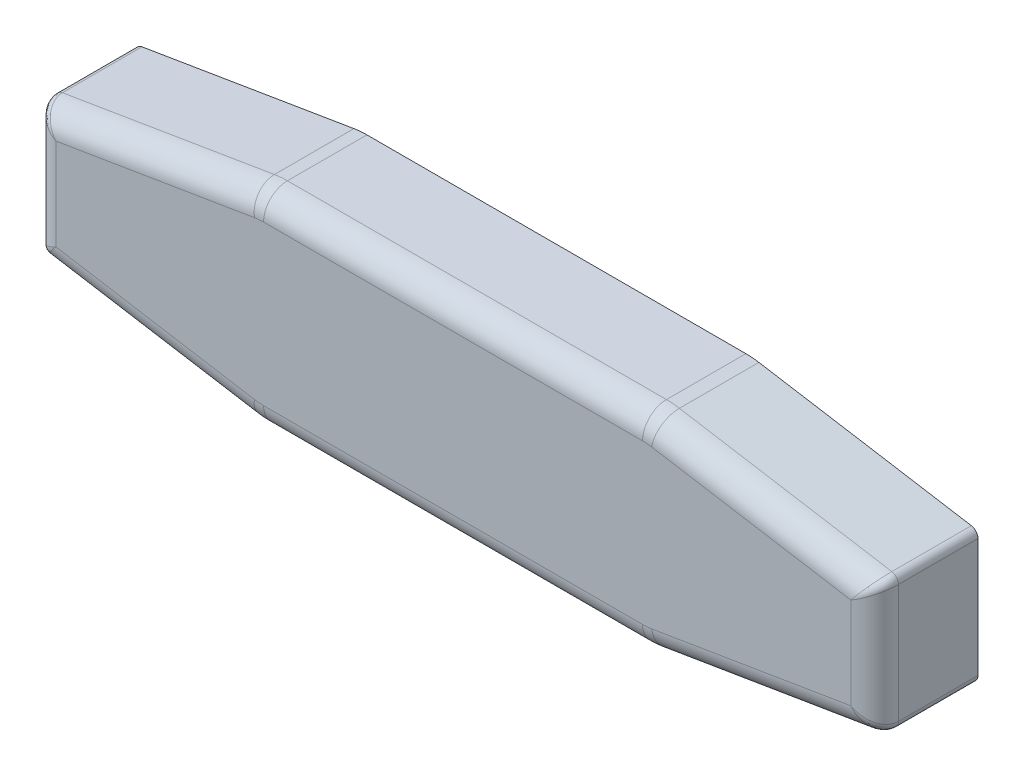
SolidWorks part; units mm, degrees
material "moto_glass"
ref_plane "Front Plane" through (0, 0, 0) normal (0, 0, 1) x (1, 0, 0)
ref_plane "Top Plane" through (0, 0, 0) normal (0, 1, 0) x (1, 0, 0)
ref_plane "Right Plane" through (0, 0, 0) normal (1, 0, 0) x (0, 0, -1)
sketch "Sketch1" plane through (0, 0, 0) normal (0, 0, 1) x (1, 0, 0)
  line L12 (-24.854, 15) -> (-55, 10)
  line L14 (55, 10) -> (24.7913, 15)
  line L16 (-24.854, 15) -> (24.7913, 15)
  line L25 (0, 0) -> (4.6771, 0)
  line L26 (55, -10) -> (24.7913, -15)
  line L27 (-24.854, -15) -> (24.7913, -15)
  line L28 (-24.854, -15) -> (-55, -10)
  line L29 (-24.6892, 13) -> (-53, 8.3044)
  line L30 (-53, 8.3044) -> (-53, -8.3044)
  line L31 (-24.6892, -13) -> (-53, -8.3044)
  line L32 (-24.6892, -13) -> (24.6269, -13)
  line L33 (53, -8.3038) -> (24.6269, -13)
  line L34 (53, 8.3038) -> (53, -8.3038)
  line L35 (53, 8.3038) -> (24.6269, 13)
  line L36 (-55, 10) -> (-55, -10)
  line L37 (55, 10) -> (55, -10)
  line L38 (-24.6892, 13) -> (24.6269, 13)
  line L39 (-24.6069, 12) -> (-52, 7.4566)
  line L40 (-52, 7.4566) -> (-52, -7.4566)
  line L41 (-24.6069, -12) -> (-52, -7.4566)
  line L42 (-24.6069, -12) -> (24.5447, -12)
  line L43 (52, -7.4557) -> (24.5447, -12)
  line L44 (52, 7.4557) -> (52, -7.4557)
  line L45 (52, 7.4557) -> (24.5447, 12)
  line L46 (-24.6069, 12) -> (24.5447, 12)
  line L47 (-24.6069, 12) -> (-24.6069, -12)
  line L48 (6.6929, 12) -> (6.6929, -12)
  line L49 (-23.6069, 12) -> (-23.6069, -12)
  line L50 (-25.6069, 11.8341) -> (-25.6069, -11.8341)
  line L51 (0, 0) -> (0, 3.5519)
  line L52 (-7.6929, 12) -> (-7.6929, -12)
  line L53 (-8.6929, 12) -> (-8.6929, -12)
  line L54 (-9.6929, 12) -> (-9.6929, -12)
  line L55 (-10.6929, 12) -> (-10.6929, -12)
  line L56 (-11.6929, 12) -> (-11.6929, -12)
  line L57 (-12.6929, 12) -> (-12.6929, -12)
  line L58 (-13.6929, 12) -> (-13.6929, -12)
  line L59 (-14.6929, 12) -> (-14.6929, -12)
  line L60 (-15.6929, 12) -> (-15.6929, -12)
  line L61 (-16.6929, 12) -> (-16.6929, -12)
  line L62 (-17.6929, 12) -> (-17.6929, -12)
  line L63 (-18.6929, 12) -> (-18.6929, -12)
  line L64 (-19.6929, 12) -> (-19.6929, -12)
  line L65 (-20.6929, 12) -> (-20.6929, -12)
  line L66 (-21.6929, 12) -> (-21.6929, -12)
  line L67 (-22.6929, 12) -> (-22.6929, -12)
  line L68 (-26.6069, 11.6683) -> (-26.6069, -11.6683)
  line L69 (-27.6069, 11.5024) -> (-27.6069, -11.5024)
  line L70 (-28.6069, 11.3366) -> (-28.6069, -11.3366)
  line L71 (-29.6069, 11.1707) -> (-29.6069, -11.1707)
  line L72 (-30.6069, 11.0048) -> (-30.6069, -11.0048)
  line L73 (-31.6069, 10.839) -> (-31.6069, -10.839)
  line L74 (-32.6069, 10.6731) -> (-32.6069, -10.6731)
  line L75 (-33.6069, 10.5073) -> (-33.6069, -10.5073)
  line L76 (-34.6069, 10.3414) -> (-34.6069, -10.3414)
  line L77 (-35.6069, 10.1755) -> (-35.6069, -10.1755)
  line L78 (-36.6069, 10.0097) -> (-36.6069, -10.0097)
  line L79 (-37.6069, 9.8438) -> (-37.6069, -9.8438)
  line L80 (-38.6069, 9.678) -> (-38.6069, -9.678)
  line L81 (-39.6069, 9.5121) -> (-39.6069, -9.5121)
  line L82 (-40.6069, 9.3463) -> (-40.6069, -9.3463)
  line L83 (-41.6069, 9.1804) -> (-41.6069, -9.1804)
  line L84 (-42.6069, 9.0145) -> (-42.6069, -9.0145)
  line L85 (-43.6069, 8.8487) -> (-43.6069, -8.8487)
  line L86 (-44.6069, 8.6828) -> (-44.6069, -8.6828)
  line L87 (-45.6069, 8.517) -> (-45.6069, -8.517)
  line L88 (-46.6069, 8.3511) -> (-46.6069, -8.3511)
  line L89 (-47.6069, 8.1852) -> (-47.6069, -8.1852)
  line L90 (-48.6069, 8.0194) -> (-48.6069, -8.0194)
  line L91 (-49.6069, 7.8535) -> (-49.6069, -7.8535)
  line L92 (-50.6069, 7.6877) -> (-50.6069, -7.6877)
  line L93 (-51.6069, 7.5218) -> (-51.6069, -7.5218)
  line L94 (-6.6929, 12) -> (-6.6929, -12)
  line L95 (-5.6929, 12) -> (-5.6929, -12)
  line L96 (-4.6929, 12) -> (-4.6929, -12)
  line L97 (-3.6929, 12) -> (-3.6929, -12)
  line L98 (-2.6929, 12) -> (-2.6929, -12)
  line L99 (-1.6929, 12) -> (-1.6929, -12)
  line L100 (-0.6929, 12) -> (-0.6929, -12)
  line L101 (5.6929, 12) -> (5.6929, -12)
  line L102 (4.6929, 12) -> (4.6929, -12)
  line L103 (3.6929, 12) -> (3.6929, -12)
  line L104 (24.6069, 12) -> (-24.5447, 12)
  line L105 (-52, 7.4557) -> (-24.5447, 12)
  line L106 (-52, 7.4557) -> (-52, -7.4557)
  line L107 (-52, -7.4557) -> (-24.5447, -12)
  line L108 (24.6069, -12) -> (-24.5447, -12)
  line L109 (24.6069, -12) -> (52, -7.4566)
  line L110 (52, 7.4566) -> (52, -7.4566)
  line L111 (24.6069, 12) -> (52, 7.4566)
  line L112 (2.6929, 12) -> (2.6929, -12)
  line L113 (1.6929, 12) -> (1.6929, -12)
  line L114 (0.6929, 12) -> (0.6929, -12)
  line L115 (7.6929, 12) -> (7.6929, -12)
  line L116 (8.6929, 12) -> (8.6929, -12)
  line L117 (9.6929, 12) -> (9.6929, -12)
  line L118 (10.6929, 12) -> (10.6929, -12)
  line L119 (11.6929, 12) -> (11.6929, -12)
  line L120 (12.6929, 12) -> (12.6929, -12)
  line L121 (13.6929, 12) -> (13.6929, -12)
  line L122 (14.6929, 12) -> (14.6929, -12)
  line L123 (15.6929, 12) -> (15.6929, -12)
  line L124 (16.6929, 12) -> (16.6929, -12)
  line L125 (17.6929, 12) -> (17.6929, -12)
  line L126 (18.6929, 12) -> (18.6929, -12)
  line L127 (19.6929, 12) -> (19.6929, -12)
  line L128 (20.6929, 12) -> (20.6929, -12)
  line L129 (21.6929, 12) -> (21.6929, -12)
  line L130 (22.6929, 12) -> (22.6929, -12)
  line L131 (23.6069, 12) -> (23.6069, -12)
  line L132 (24.6069, 12) -> (24.6069, -12)
  line L133 (25.6069, 11.8341) -> (25.6069, -11.8341)
  line L134 (26.6069, 11.6683) -> (26.6069, -11.6683)
  line L135 (27.6069, 11.5024) -> (27.6069, -11.5024)
  line L136 (28.6069, 11.3366) -> (28.6069, -11.3366)
  line L137 (29.6069, 11.1707) -> (29.6069, -11.1707)
  line L138 (30.6069, 11.0048) -> (30.6069, -11.0048)
  line L139 (31.6069, 10.839) -> (31.6069, -10.839)
  line L140 (32.6069, 10.6731) -> (32.6069, -10.6731)
  line L141 (33.6069, 10.5073) -> (33.6069, -10.5073)
  line L142 (34.6069, 10.3414) -> (34.6069, -10.3414)
  line L143 (35.6069, 10.1755) -> (35.6069, -10.1755)
  line L144 (36.6069, 10.0097) -> (36.6069, -10.0097)
  line L145 (37.6069, 9.8438) -> (37.6069, -9.8438)
  line L146 (38.6069, 9.678) -> (38.6069, -9.678)
  line L147 (39.6069, 9.5121) -> (39.6069, -9.5121)
  line L148 (40.6069, 9.3463) -> (40.6069, -9.3463)
  line L149 (41.6069, 9.1804) -> (41.6069, -9.1804)
  line L150 (42.6069, 9.0145) -> (42.6069, -9.0145)
  line L151 (43.6069, 8.8487) -> (43.6069, -8.8487)
  line L152 (44.6069, 8.6828) -> (44.6069, -8.6828)
  line L153 (45.6069, 8.517) -> (45.6069, -8.517)
  line L154 (46.6069, 8.3511) -> (46.6069, -8.3511)
  line L155 (47.6069, 8.1852) -> (47.6069, -8.1852)
  line L156 (48.6069, 8.0194) -> (48.6069, -8.0194)
  line L157 (49.6069, 7.8535) -> (49.6069, -7.8535)
  line L158 (50.6069, 7.6877) -> (50.6069, -7.6877)
  line L159 (51.6069, 7.5218) -> (51.6069, -7.5218)
  point P3 (-55, 0)
  point P7 (55, 0)
  dimension "D1" = 10
  dimension "D2" = 10
  dimension "D3" = 15
  dimension "D4" = 2
  dimension "D5" = 1
  dimension "D6" = 1
  dimension "D7" = 1
  dimension "D8" = 1
  dimension "D9" = 1
  dimension "D10" = 1
  dimension "D11" = 1
  dimension "D12" = 1
  dimension "D13" = 1
  dimension "D14" = 1
  dimension "D15" = 1
  dimension "D16" = 1
  dimension "D17" = 1
  dimension "D18" = 1
  dimension "D19" = 1
  dimension "D20" = 1
  dimension "D21" = 1
  dimension "D22" = 1
  dimension "D23" = 1
  dimension "D24" = 1
  dimension "D25" = 1
  dimension "D26" = 1
  dimension "D27" = 1
  dimension "1" = 1
  dimension "D28" = 1
  dimension "D29" = 1
  dimension "D30" = 1
  dimension "D31" = 1
  dimension "D32" = 1
  dimension "D33" = 1
  dimension "D34" = 1
  dimension "D35" = 1
  dimension "D36" = 1
  dimension "D37" = 1
  dimension "D38" = 1
  dimension "D39" = 1
  dimension "D40" = 1
  dimension "D41" = 1
  dimension "D42" = 1
  dimension "D43" = 1
  dimension "D44" = 1
  dimension "D45" = 1
  dimension "D46" = 1
  dimension "D47" = 1
  dimension "D48" = 1
  dimension "D49" = 1
  dimension "D50" = 1
  dimension "D51" = 1
  dimension "D52" = 1
  dimension "D54" = 1
  dimension "D55" = 1
extrude "Boss-Extrude5" add sketch "Sketch1" along normal blind 13 contours L38 L29 L30 L31 L32 L33 L34 L35 L104 L111 L110 L44 L109 region at (-0.0312, 12.8909, 0)
sketch "Sketch4" plane through (0, 0, 13) normal (0, 0, 1) x (1, 0, 0)
  line L16 (52, 7.4566) -> (24.6069, 12)
  line L17 (52, -7.4566) -> (52, 7.4566)
  line L18 (24.6069, -12) -> (52, -7.4566)
  line L19 (-24.6069, -12) -> (24.6069, -12)
  line L20 (-52, -7.4566) -> (-24.6069, -12)
  line L21 (-52, 7.4566) -> (-52, -7.4566)
  line L22 (-24.6069, 12) -> (-52, 7.4566)
  line L23 (24.6069, 12) -> (-24.6069, 12)
  line L24 (52, 7.4566) -> (24.6069, 12)
  line L25 (52, -7.4566) -> (52, 7.4566)
  line L26 (24.6069, -12) -> (52, -7.4566)
  line L27 (-24.6069, -12) -> (24.6069, -12)
  line L28 (-52, -7.4566) -> (-24.6069, -12)
  line L29 (-52, 7.4566) -> (-52, -7.4566)
  line L30 (-24.6069, 12) -> (-52, 7.4566)
  line L31 (24.6069, 12) -> (-24.6069, 12)
  dimension "D1" = 0
extrude "Boss-Extrude7" add sketch "Sketch4" against normal blind 1
fillet "Fillet1" radius 3 16 edges at (38.8134, 10.6519, 13) (53, 0, 13) (38.8134, -10.6519, 13) (-0.0312, -13, 13) (-38.8446, -10.6522, 13) (-53, 0, 13) (-38.8446, 10.6522, 13) (-0.0312, 13, 13) (-38.3034, 9.7283, 12) (-52, 0, 12) (-38.3034, -9.7283, 12) (0, -12, 12) (38.3034, -9.7283, 12) (52, 0, 12) (38.3034, 9.7283, 12) (0, 12, 12)
fillet "Fillet2" radius 10 8 edges at (-24.6169, -12.1213, 12.1213) (24.5546, -12.1213, 12.1213) (24.5546, 12.1213, 12.1213) (-24.6169, 12.1213, 12.1213) (-24.6892, 13, 5) (24.6269, 13, 5) (24.6269, -13, 5) (-24.6892, -13, 5)
fillet "Fillet3" radius 10 8 edges at (24.5345, 11.1213, 11.1213) (24.5345, -11.1213, 11.1213) (-24.5345, -11.1213, 11.1213) (-24.5345, 11.1213, 11.1213) (-24.6069, 12, 4.5) (-24.6069, -12, 4.5) (24.6069, -12, 4.5) (24.6069, 12, 4.5)
fillet "Fillet4" radius 1 16 edges at (52, 7.4566, 4.5) (52, -7.4566, 4.5) (53, -8.3038, 5) (53, 8.3038, 5) (-53, -8.3044, 5) (-53, 8.3044, 5) (-52, -7.4566, 4.5) (-52, 7.4566, 4.5) (51.1213, 6.7116, 11.1213) (51.1213, -6.7116, 11.1213) (52.1213, -7.5586, 12.1213) (52.1213, 7.5586, 12.1213) (-52.1213, -7.5594, 12.1213) (-52.1213, 7.5594, 12.1213) (-51.1213, -6.7116, 11.1213) (-51.1213, 6.7116, 11.1213)
